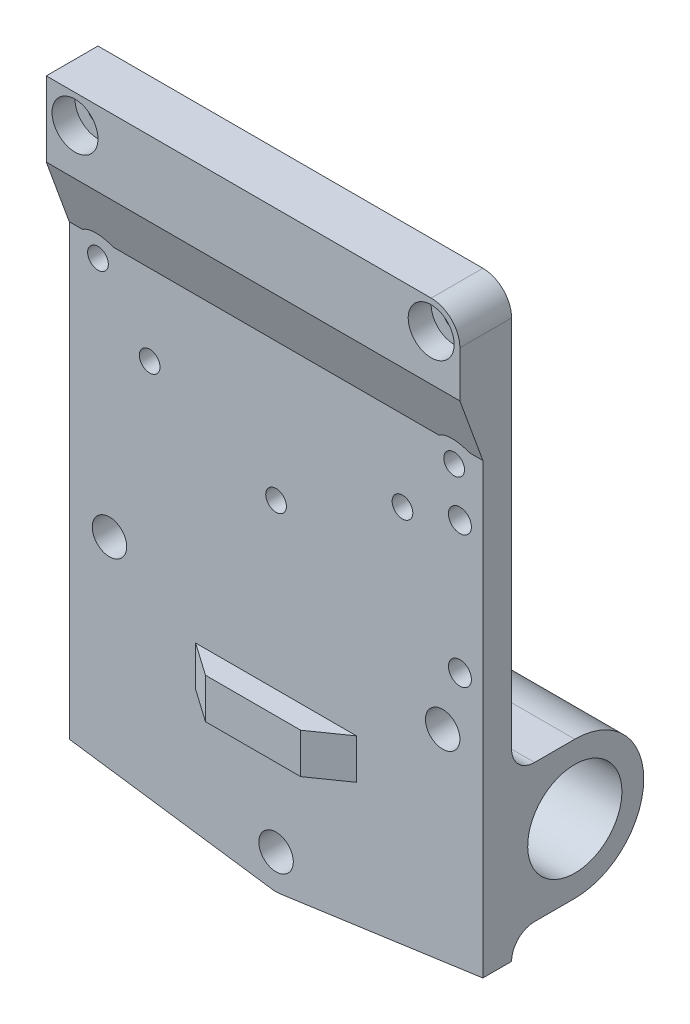
SolidWorks part; units mm, degrees
ref_plane "Front Plane" through (0, 0, 0) normal (0, 0, 1) x (1, 0, 0)
ref_plane "Top Plane" through (0, 0, 0) normal (0, 1, 0) x (1, 0, 0)
ref_plane "Right Plane" through (0, 0, 0) normal (1, 0, 0) x (0, 0, -1)
sketch "Sketch1" plane through (0, 0, 0) normal (0, 0, 1) x (1, 0, 0)
  line L0 (-36, 51) -> (36, -51) construction
  line L1 (-36, 51) -> (36, 51)
  line L2 (-36, 51) -> (-36, -51)
  line L3 (-36, -51) -> (36, -51)
  line L4 (36, 51) -> (36, -51)
  dimension "D1" = 102
  dimension "D2" = 72
extrude "Boss-Extrude1" add sketch "Sketch1" along normal blind 5
sketch "Sketch12" plane through (-36, 0, 0) normal (-1, 0, 0) x (0, 0, 1)
  line L0 (5, 51) -> (9, 51)
  line L1 (9, 51) -> (9, 38)
  line L2 (9, 38) -> (5, 27.0101)
  line L3 (5, 51) -> (5, -51) construction
  line L4 (5, 27.0101) -> (5, 51)
  dimension "D1" = 4
  dimension "D2" = 13
  dimension "D3" = 20
extrude "Boss-Extrude4" add sketch "Sketch12" against normal up to surface (72 mm away) up to face at (36, 0, 2.5)
sketch "Sketch7" plane through (0, 0, 0) normal (0, 0, -1) x (-1, 0, 0)
  line L0 (-36, -51) -> (-36, 51) construction
  line L1 (-36, 51) -> (36, 51) construction
  line L2 (36, 51) -> (36, -51) construction
  circle A0 centre (31, 24) radius 1.8
  circle A3 centre (31, 46) radius 1.8
  circle A10 centre (-31, 24) radius 1.8
  circle A11 centre (-31, 46) radius 1.8
  circle A12 centre (0, 3) radius 1.8
  circle A13 centre (22, 13) radius 1.8
  circle A14 centre (-22, 13) radius 1.8
  dimension "D7" = 3.6
  dimension "D1" = 5
  dimension "D2" = 5
  dimension "D3" = 22
  dimension "D4" = 5
  dimension "D5" = 14
  dimension "D6" = 14
  dimension "D8" = 48
  dimension "D9" = 38
extrude "Cut-Extrude4" cut sketch "Sketch7" against normal through all
sketch "Sketch8" plane through (36, 0, 0) normal (1, 0, 0) x (0, 0, -1)
  line L0 (11, -23) -> (0, -23)
  line L1 (0, -51) -> (0, 51) construction
  line L2 (0, -23) -> (0, -47)
  line L3 (0, -47) -> (11, -47)
  line L4 (-5, -51) -> (0, -51) construction
  circle A0 centre (11, -35) radius 8.2
  arc A1 (11, -47) -> (11, -23) centre (11, -35) ccw
  dimension "D1" = 16.4
  dimension "D4" = 12
  dimension "D2" = 11
  dimension "D3" = 16
extrude "Boss-Extrude2" add sketch "Sketch8" against normal up to surface (72 mm away) up to face at (-36, 16.42, 4.3333)
sketch "Sketch9" plane through (0, 0, 0) normal (0, 0, -1) x (-1, 0, 0)
  line L0 (36, -35) -> (-36, -35) construction
  circle A0 centre (-29, -17) radius 5 construction
  circle A1 centre (29, -17) radius 5 construction
  circle A2 centre (0, -50) radius 5 construction
  circle A3 centre (-29, -17) radius 3
  circle A4 centre (29, -17) radius 3
  circle A5 centre (0, -50) radius 3
  dimension "D1" = 10
  dimension "D2" = 18
  dimension "D6" = 6
  dimension "D3" = 15
  dimension "D4" = 29
  dimension "D5" = 29
extrude "Cut-Extrude5" cut sketch "Sketch9" against normal through all and the other way through all
sketch "Sketch10" plane through (0, 0, 0) normal (0, 0, -1) x (-1, 0, 0)
  line L0 (36, -51) -> (2.8284, -51) construction
  line L1 (36, -51) -> (2.8284, -51)
  line L2 (-36, -51) -> (-0.835, -55.9416)
  line L3 (-36, -51) -> (-2.8284, -51)
  line L4 (0, -47) -> (-36, -47)
  line L5 (-36, -47) -> (-36, -51)
  line L6 (-36, -51) -> (-2.8284, -51)
  line L8 (0.835, -55.9416) -> (36, -51)
  arc A0 (-0.835, -55.9416) -> (0.835, -55.9416) centre (0, -50) ccw
  arc A1 (0, -47) -> (-2.8284, -51) centre (0, -50) ccw
  arc A2 (-2.8284, -51) -> (2.8284, -51) centre (0, -50) ccw
  dimension "D2" = 12
  dimension "D1" = 0
extrude "Boss-Extrude3" add sketch "Sketch10" against normal up to surface (5 mm away) up to face at (6, -24.33, 5)
sketch "Sketch11" plane through (0, 0, 0) normal (0, 0, -1) x (-1, 0, 0)
  circle A0 centre (-29, -17) radius 5.5
  circle A1 centre (29, -17) radius 5.5
  circle A2 centre (0, -50) radius 5.5
  dimension "D1" = 11
extrude "Cut-Extrude6" cut sketch "Sketch11" along normal through all
fillet "Fillet1" radius 4 3 edges
sketch "Sketch13" plane through (0, 0, 5) normal (0, 0, 1) x (1, 0, 0)
  circle A0 centre (-31, 24) radius 4
  circle A1 centre (31, 24) radius 4
  circle A2 centre (31, 46) radius 4
  circle A3 centre (-31, 46) radius 4
  dimension "D1" = 8
extrude "Cut-Extrude7" cut sketch "Sketch13" along normal through all
sketch "Sketch14" plane through (0, 0, 5) normal (0, 0, 1) x (1, 0, 0)
  line L0 (-36, -35) -> (36, -35) construction
  line L1 (36, -51) -> (36, 27.0101) construction
  circle A0 centre (32, 16) radius 2
  circle A1 centre (32, -7) radius 2
  dimension "D1" = 4
  dimension "D2" = 51
  dimension "D3" = 28
  dimension "D4" = 4
extrude "Cut-Extrude8" cut sketch "Sketch14" against normal through all
sketch "Sketch15" plane through (0, 0, 0) normal (0, 1, 0) x (1, 0, 0)
  line L0 (-14, -5) -> (14, -5)
  line L2 (14, -5) -> (8.2874, -9)
  line L3 (8.2874, -9) -> (-8.2874, -9)
  line L4 (-8.2874, -9) -> (-14, -5)
  line L5 (-0.835, -5) -> (-36, -5) construction
  dimension "D1" = 35
  dimension "D2" = 35
  dimension "D3" = 14
  dimension "D4" = 14
  dimension "D5" = 4
extrude "Boss-Extrude5" add sketch "Sketch15" against normal blind 7 from offset 25.5 separate body offset against normal yes
fillet "Fillet2" radius 5 1 edges at (36, 51, 4.5)
